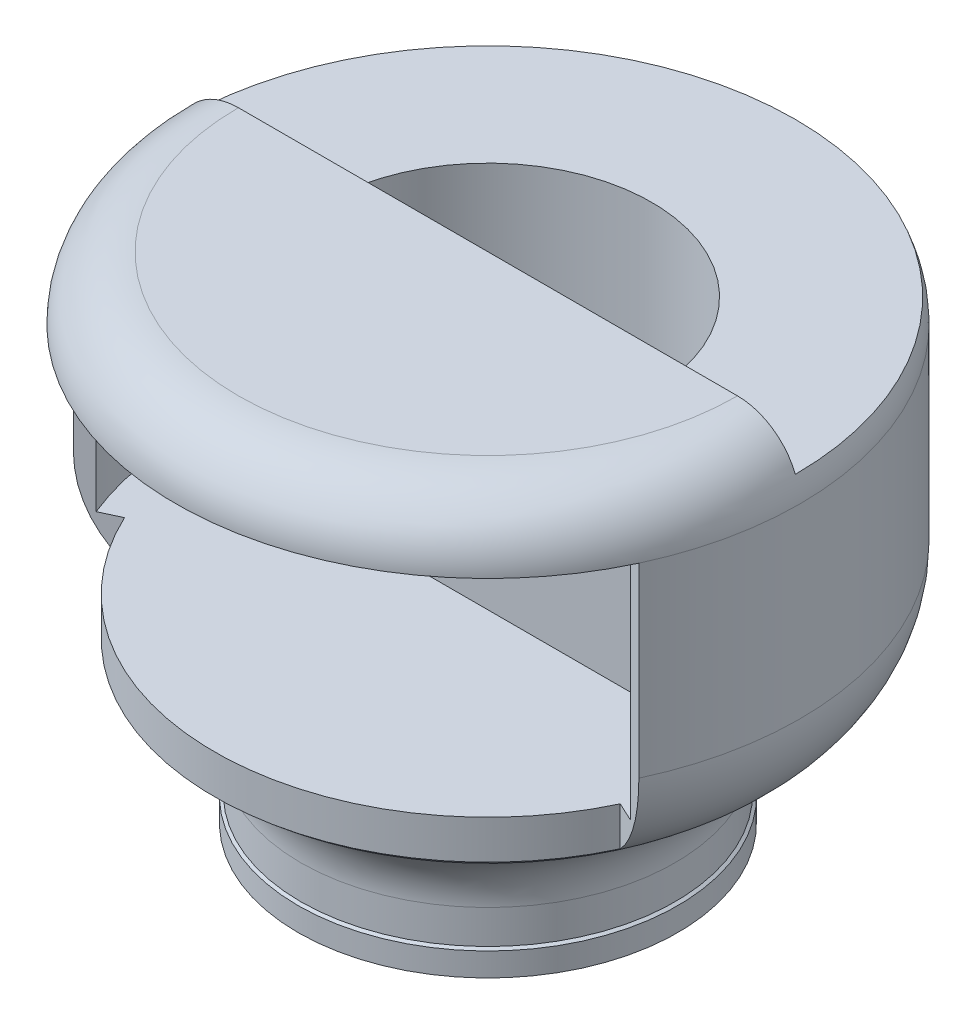
SolidWorks part; units mm, degrees
ref_plane "Front Plane" through (0, 0, 0) normal (0, 0, 1) x (1, 0, 0)
ref_plane "Top Plane" through (0, 0, 0) normal (0, 1, 0) x (1, 0, 0)
ref_plane "Right Plane" through (0, 0, 0) normal (1, 0, 0) x (0, 0, -1)
sketch "Sketch1" plane through (0, 0, 0) normal (0, 0, 1) x (1, 0, 0)
  line L0 (0, 0) -> (0, 90.2242) construction
  line L28 (0, 63.4279) -> (32, 63.4279)
  line L29 (40, 55.4279) -> (40, 31.5563)
  line L30 (22.5, 0) -> (24.35, 0)
  line L31 (24.35, 0) -> (24.35, 3)
  line L32 (24.35, 3) -> (24, 3.25)
  line L33 (24, 3.25) -> (24, 7.5811)
  line L34 (28.5399, 15.9588) -> (33.1902, 18.9896)
  line L35 (0, 13) -> (22, 13)
  line L36 (22.5, 12.5) -> (22.5, 0)
  line L37 (0, 13) -> (0, 63.4279)
  arc A0 (22, 13) -> (22.5, 12.5) centre (22, 12.5) cw
  arc A1 (24, 7.5811) -> (28.5399, 15.9588) centre (34, 7.5811) cw
  arc A2 (33.1902, 18.9896) -> (40, 31.5563) centre (25, 31.5563) ccw
  arc A3 (32, 63.4279) -> (40, 55.4279) centre (32, 55.4279) cw
  point P11 (22.9, 63.4279)
  point P18 (22.5, 13)
  point P21 (24, 13)
  point P24 (40, 23.4279)
  point P27 (40, 63.4279)
  point P28 (28.5604, 23.4279)
  point P31 (22.5, 17)
  dimension "D8" = 9.75
  dimension "D9" = 0.5
  dimension "D4" = 1.85
  dimension "D1" = 22.5
  dimension "D10" = 10
  dimension "D11" = 15
  dimension "D12" = 8
  dimension "D2" = 40
  dimension "D3" = 40
  dimension "D5" = 1.5
  dimension "D6" = 3
  dimension "D7" = 13
revolve "Revolve1" add sketch "Sketch1" angle 360 about L0
ref_plane "Plane1" through (0, 13, 0) normal (0, -1, 0) x (-1, 0, 0)
sketch "Sketch18" plane through (0, 0, 0) normal (0, 0, 1) x (1, 0, 0)
  line L0 (0, 0) -> (0, 101.5813) construction
  line L1 (-24.35, 0) -> (24.35, 0) construction
sketch "Sketch3" plane through (0, 0, 0) normal (0, 0, 1) x (1, 0, 0)
  point P0 (1.2404, 19.1989)
ref_point "Point1"
ref_plane "Plane2" through (0, 0, 22.9) normal (0, 0, 1) x (1, 0, 0)
ref_plane "Plane3" through (0, 0, 40) normal (0, 0, 1) x (1, 0, 0)
ref_plane "Plane4" through (0, 55.4279, 0) normal (0, 1, 0) x (1, 0, 0)
sketch "Sketch9" plane through (0, 55.4279, 0) normal (0, 1, 0) x (1, 0, 0)
  line L1 (-24, -1.7631) -> (24, -1.7631)
  arc A2 (-37, -1.6015) -> (37, -2.3985) centre (0, -2) ccw
  arc A3 (-37, -1.6015) -> (37, -2.3985) centre (0, -2) cw
  arc A6 (-24, -1.7631) -> (24, -1.7631) centre (0, -0.0603) cw
  dimension "D1" = 74
  dimension "D3" = 13
  dimension "D4" = 13
ref_plane "Plane5" through (0, 13, 0) normal (0, -1, 0) x (-1, 0, 0)
sketch "Sketch11" plane through (0, 13, 0) normal (0, -1, 0) x (-1, 0, 0)
  line L0 (-21, 0) -> (21, 0)
  arc A1 (-21, 0) -> (21, 0) centre (0, 0) cw
  dimension "D1" = 42
extrude "Cut-Extrude3" cut sketch "Sketch11" against normal blind 60
ref_plane "Plane6" through (0, 0, -40) normal (0, 0, -1) x (-1, 0, 0)
extrude "Cut-Extrude5" cut sketch "Sketch9" against normal blind 30 and the other way blind 2
sketch "Sketch19" plane through (0, 0, 0) normal (1, 0, 0) x (0, 0, -1)
  line L0 (-47.0647, 55.4279) -> (-35.0647, 55.4279)
  line L1 (44, 55.4279) -> (-44, 55.4279) construction
  line L2 (-35.0647, 55.4279) -> (-35.0647, 18.9279)
  line L3 (-35.0647, 18.9279) -> (-47.0647, 18.9279)
  line L4 (-47.0647, 18.9279) -> (-47.0647, 55.4279)
  dimension "D1" = 12
  dimension "D2" = 36.5
revolve "Cut-Revolve2" cut sketch "Sketch19" angle 65 about L0 other way angle 65
ref_plane "Plane7" through (0, 0, 22.5) normal (0, 0, -1) x (-1, 0, 0)
sketch "Sketch21" plane through (0, 0, 22.5) normal (0, 0, -1) x (-1, 0, 0)
  line L0 (0, 0) -> (0, 101.5813) construction
  line L1 (-1.625, 4) -> (1.625, 4)
  line L2 (-1.625, 4) -> (-1.625, 0)
  line L3 (-1.625, 0) -> (1.625, 0)
  line L4 (1.625, 4) -> (1.625, 0)
  line L5 (-1.625, 4) -> (1.625, 0) construction
  line L6 (-1.625, 0) -> (1.625, 4) construction
  line L7 (-22.5, 0) -> (22.5, 0) construction
  point P0 (0, 2)
  dimension "D1" = 4
  dimension "D2" = 3.25
extrude "Boss-Extrude3" add sketch "Sketch21" along normal blind 1.35
pattern_circular "CirPattern1" count 5 over 360 about axis through (0, 0, 0) along (0, -1, 0) of "Boss-Extrude3"
ref_plane "Plane8" through (0, 18.9896, 0) normal (0, 1, 0) x (1, 0, 0)
sketch "Sketch22" plane through (0, 63.4279, 0) normal (0, 1, 0) x (1, 0, 0)
  line L0 (-40, 0) -> (40, 0)
  arc A0 (-40, 0) -> (40, 0) centre (0, 0) cw
  arc A1 (36.2523, -16.9047) -> (-36.2523, -16.9047) centre (0, 0) ccw construction
extrude "Cut-Extrude9" cut sketch "Sketch22" against normal blind 5
